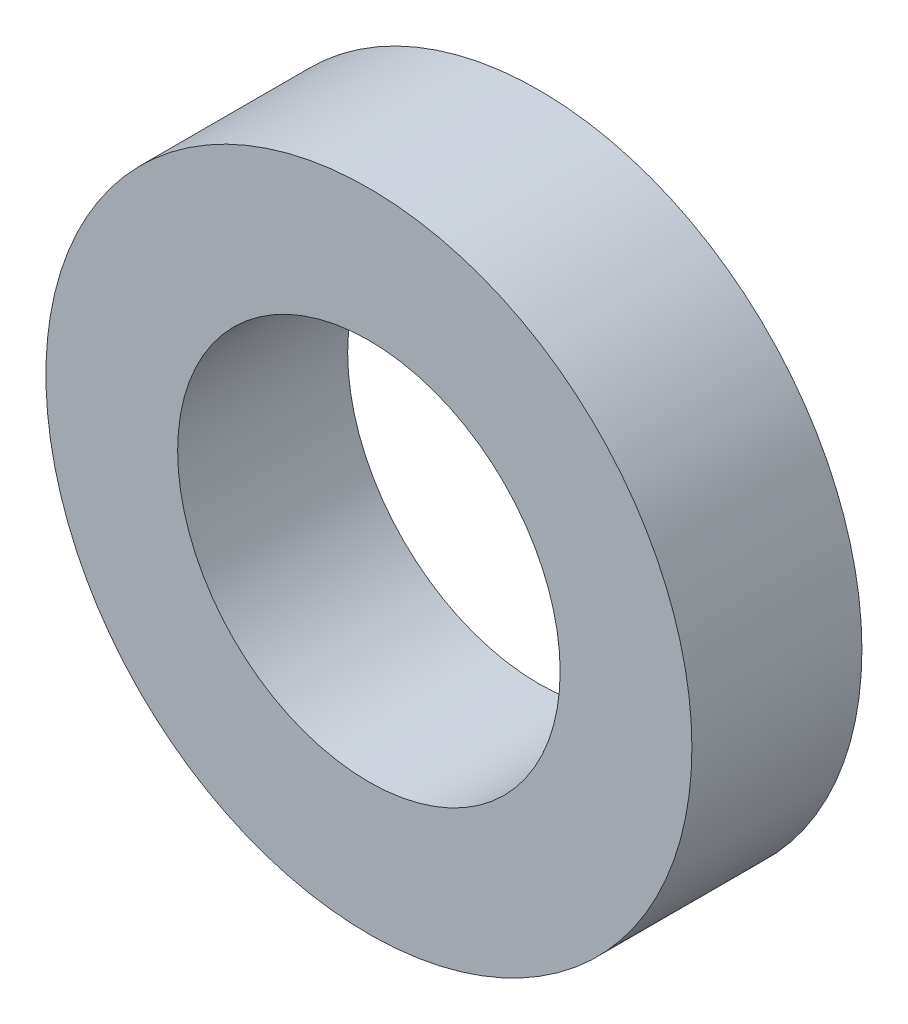
SolidWorks part; units mm, degrees
ref_plane "Front Plane" through (0, 0, 0) normal (0, 0, 1) x (1, 0, 0)
ref_plane "Top Plane" through (0, 0, 0) normal (0, 1, 0) x (1, 0, 0)
ref_plane "Right Plane" through (0, 0, 0) normal (1, 0, 0) x (0, 0, -1)
sketch "Sketch1" plane through (0, 0, 0) normal (0, 0, 1) x (1, 0, 0)
  circle A0 centre (0, 0) radius 24.13
  circle A1 centre (0, 0) radius 14.2875
extrude "Boss-Extrude1" add sketch "Sketch1" along normal mid plane 12.7
sketch "Sketch2" plane through (0, 0, 6.35) normal (0, 0, 1) x (1, 0, 0)
  circle A0 centre (0, 0) radius 20.447
  circle A1 centre (0, 0) radius 14.2875
